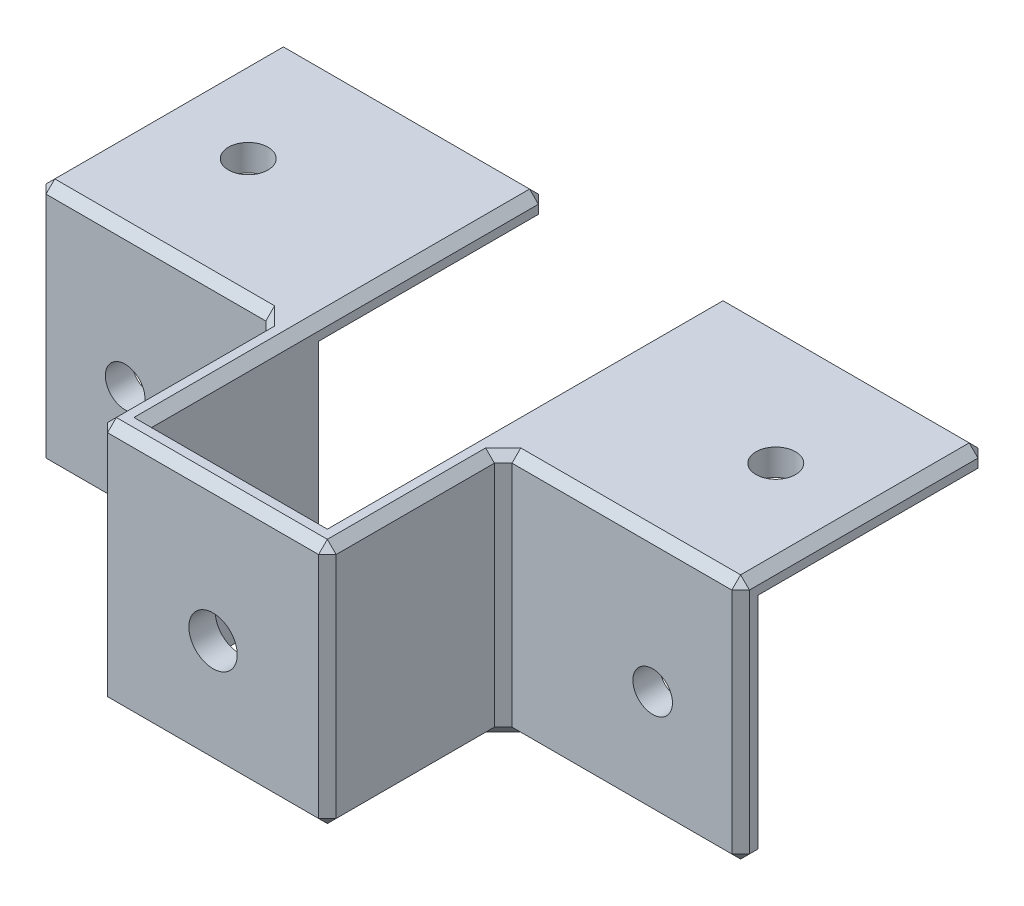
SolidWorks part; units mm, degrees
ref_plane "Front Plane" through (0, 0, 0) normal (0, 0, 1) x (1, 0, 0)
ref_plane "Top Plane" through (0, 0, 0) normal (0, 1, 0) x (1, 0, 0)
ref_plane "Right Plane" through (0, 0, 0) normal (1, 0, 0) x (0, 0, -1)
sketch "Sketch2" plane through (0, 0, 0) normal (0, 0, 1) x (1, 0, 0)
  line L0 (-40, 12.5) -> (-10, 12.5)
  line L1 (-10, 12.5) -> (-10, -12.5)
  line L2 (-10, -12.5) -> (-40, -12.5)
  line L3 (-40, -12.5) -> (-40, 12.5)
  line L4 (-10, 12.5) -> (10, 12.5)
  line L5 (10, 12.5) -> (10, -12.5)
  line L6 (10, -12.5) -> (-10, -12.5)
  line L7 (10, 12.5) -> (40, 12.5)
  line L8 (40, 12.5) -> (40, -12.5)
  line L9 (40, -12.5) -> (10, -12.5)
  line L10 (-13, 12.5) -> (-13, -12.5)
  line L11 (13, 12.5) -> (13, -12.5)
  point P3 (30, 0)
  point P10 (-30, 0)
  point P11 (0, 0)
  point P15 (-40, 0)
  point P19 (0, 12.5)
  dimension "D1" = 20
  dimension "D2" = 20
  dimension "D3" = 25
  dimension "D4" = 10
  dimension "D5" = 3
  dimension "D6" = 3
extrude "Boss-Extrude1" add sketch "Sketch2" against normal blind 3 contours L10 L0 L3 L2 | L7 L11 L9 L8 | L0 L10 L2 L1 | L11 L7 L5 L9 region at (-26.5, 0, 0) region at (-11.5, 0, 0) region at (11.5, 0, 0) region at (26.5, 0, 0)
extrude "Boss-Extrude2" add sketch "Sketch2<3>" along normal blind 20 contours L0 L10 L2 L1 | L11 L7 L5 L9 region at (-11.5, 0, 0) region at (11.5, 0, 0)
sketch "Sketch2<3>" plane through (0, 0, 0) normal (0, 0, 1) x (1, 0, 0) same geometry as "Sketch2"
extrude "Boss-Extrude3" add sketch "Sketch2<4>" against normal blind 3 from surface contours L6 L5 L4 L1 region at (0, 0, 0) starting at face at (-11.5, 0, 20)
sketch "Sketch2<4>" plane through (0, 0, 0) normal (0, 0, 1) x (1, 0, 0) same geometry as "Sketch2"
sketch "Sketch3" plane through (0, 0, 0) normal (0, 1, 0) x (1, 0, 0)
  line L0 (-40, 0) -> (-40, 28)
  line L1 (-40, 28) -> (-13, 28)
  line L10 (0, -1000) -> (0, 49000) construction
  line L11 (10, 0) -> (-10, 0) construction
  line L13 (-13, 28) -> (-13, 0)
  line L14 (-13, 0) -> (-40, 0)
  line L15 (-13, 28) -> (-10, 28)
  line L16 (-10, 28) -> (-10, 0)
  line L17 (-10, 0) -> (-40, 0) construction
  line L18 (-10, 3) -> (-10, -17) construction
  line L19 (-10, 0) -> (-13, 0)
  line L20 (10, 0) -> (13, 0)
  line L21 (10, 28) -> (10, 0)
  line L22 (13, 28) -> (10, 28)
  line L23 (13, 0) -> (40, 0)
  line L24 (13, 28) -> (13, 0)
  line L25 (40, 28) -> (13, 28)
  line L26 (40, 0) -> (40, 28)
  line L27 (13, -20) -> (13, 0) construction
  line L28 (10, 3) -> (10, -17) construction
  line L29 (-13, -20) -> (13, -20) construction
  line L30 (10, -17) -> (-10, -17) construction
  line L31 (-13, -20) -> (-13, 0) construction
  line L32 (13, -20) -> (13, 0)
  line L33 (10, 3) -> (10, -17)
  line L34 (-13, -20) -> (13, -20)
  line L35 (10, -17) -> (-10, -17)
  line L36 (-10, 3) -> (-10, -17)
  line L37 (-13, -20) -> (-13, 0)
  point P9 (0, 0)
  point P15 (-40, 3)
  point P17 (-30, 14)
  point P19 (-40, 14)
  point P29 (30, 14)
  point P30 (40, 3)
  dimension "D1" = 25
extrude "Boss-Extrude4" add sketch "Sketch3" along normal blind 3 from surface contours L14 L13 L1 L0 | L19 L16 L15 L13 | L24 L22 L21 L20 | L23 L26 L25 L24 | L34 L10 L35 L36 L19 L37 | L10 L34 L32 L20 L33 L35 region at (-26.5, 0, -14) region at (-11.5, 0, -14) region at (-11.5, 0, 0.2385) region at (0.2385, 0, 18.5) region at (26.5, 0, -14) region at (11.5, 0, -14) starting at face at (0, 12.5, 5.1667)
sketch "Sketch5" plane through (0, 0, 20) normal (0, 0, 1) x (1, 0, 0)
  point P0 (0, 0)
hole_wizard "CBORE for M5 Hex Head Cap Screw1" positions "Sketch5" profile "Sketch6" counterbore size "M5" standard "ANSI Metric"
sketch "Sketch6" plane through (0, 0, 20) normal (1, 0, 0) x (0, -1, 0)
  line L0 (0, 0) -> (0, 4.6524)
  line L1 (0, 4.6524) -> (2.75, 3)
  line L2 (2.75, 3) -> (2.75, 3.65)
  line L3 (2.75, 3.65) -> (2.7505, 3.65)
  line L4 (2.7505, 3.65) -> (2.7505, 0)
  line L5 (2.7505, 0) -> (0, 0)
  line L10 (0, 4.6524) -> (-2.75, 3) construction
  line L11 (0, -6.35) -> (0, 107.95) construction
  dimension "Hole Dia." = 5.5
  dimension "Hole Depth" = 3
  dimension "C'Bore Dia." = 5.501
  dimension "C'Bore Depth" = 3.65
  dimension "Drill Angle" = 118
sketch "Sketch9" plane through (0, 0, 0) normal (0, 0, 1) x (1, 0, 0)
  point P0 (30, 0)
  point P2 (-30, 0)
hole_wizard "CBORE for M4 SHCS1" positions "Sketch9" profile "Sketch10" counterbore size "M4" standard "ANSI Metric"
sketch "Sketch10" plane through (30, 0, 0) normal (1, 0, 0) x (0, -1, 0)
  line L0 (0, 0) -> (0, 11.3519)
  line L1 (0, 11.3519) -> (2.25, 10)
  line L2 (2.25, 10) -> (2.25, 4)
  line L3 (2.25, 4) -> (2.251, 4)
  line L4 (2.251, 4) -> (2.251, 0)
  line L5 (2.251, 0) -> (0, 0)
  line L10 (0, 11.3519) -> (-2.25, 10) construction
  line L11 (0, -6.35) -> (0, 107.95) construction
  dimension "Hole Dia." = 4.5
  dimension "Hole Depth" = 10
  dimension "C'Bore Dia." = 4.502
  dimension "C'Bore Depth" = 4
  dimension "Drill Angle" = 118
sketch "Sketch11" plane through (0, 15.5, 0) normal (0, 1, 0) x (1, 0, 0)
  point P0 (30, 14)
  point P2 (-30, 14)
hole_wizard "CBORE for M4 SHCS2" positions "Sketch11" profile "Sketch12" counterbore size "M4" standard "ANSI Metric"
sketch "Sketch12" plane through (30, 15.5, -14) normal (1, 0, 0) x (0, 0, 1)
  line L0 (0, 0) -> (0, 11.3519)
  line L1 (0, 11.3519) -> (2.25, 10)
  line L2 (2.25, 10) -> (2.25, 4)
  line L3 (2.25, 4) -> (2.2515, 4)
  line L4 (2.2515, 4) -> (2.2515, 0)
  line L5 (2.2515, 0) -> (0, 0)
  line L10 (0, 11.3519) -> (-2.25, 10) construction
  line L11 (0, -6.35) -> (0, 107.95) construction
  dimension "Hole Dia." = 4.5
  dimension "Hole Depth" = 10
  dimension "C'Bore Dia." = 4.503
  dimension "C'Bore Depth" = 4
  dimension "Drill Angle" = 118
chamfer "Chamfer1" distance 1 angle 45 44 edges at (-40, -12.5, -1.5) (-10, -12.5, 7) (-40, 0, -3) (-25, -12.5, -3) (-10, 0, -3) (-40, 1.5, 0) (-26.5, -12.5, 0) (-13, -12.5, 10) (0, -12.5, 20) (-13, 1.5, 20) (-13, 1.5, 0) (0, -12.5, 17) (40, -12.5, -1.5) (10, -12.5, 7) (40, 0, -3) (25, -12.5, -3) (10, 0, -3) (40, 1.5, 0) (26.5, -12.5, 0) (13, -12.5, 10) (13, 1.5, 20) (13, 1.5, 0) (40, 14, -28) (40, 12.5, -15.5) (25, 12.5, -28) (10, 12.5, -15.5) (10, 14, -28) (-10, 14, -28) (0, 15.5, 20) (13, 15.5, 10) (26.5, 15.5, 0) (40, 15.5, -14) (25, 15.5, -28) (10, 15.5, -5.5) (0, 15.5, 17) (-10, 15.5, -5.5) (-25, 15.5, -28) (-13, 15.5, 10) (-26.5, 15.5, 0) (-40, 15.5, -14) (-40, 14, -28) (-10, 12.5, -15.5) (-25, 12.5, -28) (-40, 12.5, -15.5)
